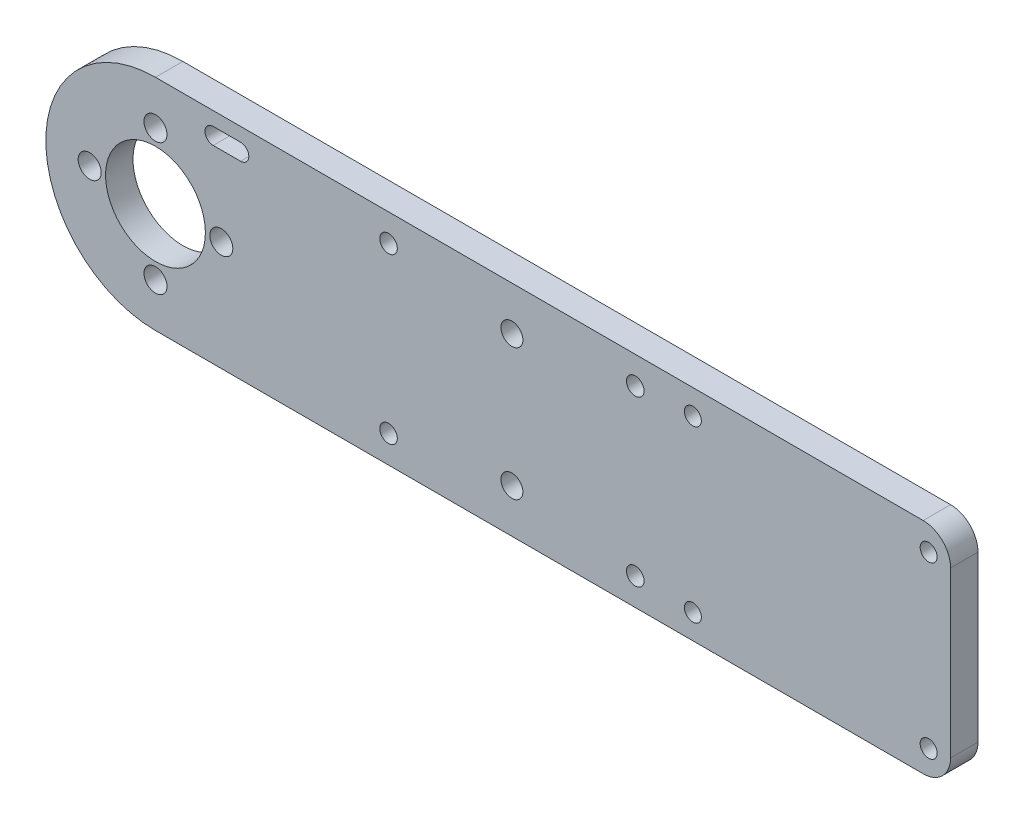
SolidWorks part; units mm, degrees
material "Acrylic (Medium-high impact)"
ref_plane "Front Plane" through (0, 0, 0) normal (0, 0, 1) x (1, 0, 0)
ref_plane "Top Plane" through (0, 0, 0) normal (0, 1, 0) x (1, 0, 0)
ref_plane "Right Plane" through (0, 0, 0) normal (1, 0, 0) x (0, 0, -1)
sketch "Sketch2" plane through (0, 0, 0) normal (0, 0, 1) x (1, 0, 0)
  line L0 (0, 20) -> (0, -20)
  line L1 (0, 20) -> (145, 20)
  line L2 (0, -20) -> (145, -20)
  line L3 (145, 20) -> (145, -20)
  line L4 (0, 0) -> (-20, 0)
  circle A0 centre (0, 0) radius 20
  circle A1 centre (0, 0) radius 9.1
  dimension "D1" = 40
  dimension "D3" = 18.2
  dimension "D2" = 165
extrude "Boss-Extrude1" add sketch "Sketch2" along normal mid plane 5 contours A1 L0 A0 | A0 L2 L3 L1 | A1 L4 A0 L0 | A1 L0 A0 L4 region at (9.696, 0, 0) region at (80.2769, 0, 0) region at (-9.696, 9.696, 0) region at (-9.696, -9.696, 0)
fillet "Fillet1" radius 5 2 edges at (145, -20, 0) (145, 20, 0)
sketch "Sketch3" plane through (0, 0, -2.5) normal (0, 0, -1) x (-1, 0, 0)
  line L0 (-119.5, 20) -> (-119.5, -20)
  line L1 (-119.5, 0) -> (-98, 0)
  line L2 (-98, 0) -> (-98, 15.5)
  line L3 (-145, 15) -> (-145, -15)
  line L4 (-140, -20) -> (0, -20)
  line L5 (0, 20) -> (-140, 20)
  line L6 (-145, 15) -> (-145, -15)
  line L7 (-140, -20) -> (0, -20)
  line L8 (0, 20) -> (-140, 20)
  line L9 (-119.5, 0) -> (-65, 0)
  line L10 (-65, 0) -> (-65, 15)
  line L11 (-65, 15) -> (-87.5, 15)
  line L12 (0, 0) -> (0, 12)
  line L13 (0, 0) -> (-65, 0)
  line L14 (-15.5185, 16) -> (-10.5185, 16) construction
  line L17 (-15.5185, 17.5) -> (-10.5185, 17.5)
  line L18 (-15.5185, 14.5) -> (-10.5185, 14.5)
  line L19 (0, 0) -> (18.4819, 0)
  line L20 (-65, 0.6163) -> (-65, 6.1951)
  line L21 (-65, 0) -> (-65, 12)
  circle A0 centre (0, 0) radius 12
  circle A1 centre (-98, 15.5) radius 1.55
  circle A2 centre (-98, -15.5) radius 1.55
  arc A3 (-145, -15) -> (-140, -20) centre (-140, -15) ccw
  arc A4 (0, -20) -> (0, 20) centre (0, 0) ccw
  arc A5 (-140, 20) -> (-145, 15) centre (-140, 15) ccw
  arc A6 (-145, -15) -> (-140, -20) centre (-140, -15) ccw
  arc A7 (0, -20) -> (0, 20) centre (0, 0) ccw
  arc A8 (-140, 20) -> (-145, 15) centre (-140, 15) ccw
  circle A9 centre (-141, -15.5) radius 1.55
  circle A10 centre (-141, 15.5) radius 1.55
  circle A11 centre (-87.5, 15) radius 1.6
  circle A12 centre (-87.5, -15) radius 1.6
  circle A13 centre (-42.5, -15) radius 1.6
  circle A14 centre (-42.5, 15) radius 1.6
  circle A15 centre (0, 12) radius 2.1
  circle A16 centre (12, 0) radius 2.1
  circle A17 centre (0, -12) radius 2.1
  circle A18 centre (-12, 0) radius 2.1
  arc A21 (-15.5185, 17.5) -> (-15.5185, 14.5) centre (-15.5185, 16) ccw
  arc A22 (-10.5185, 14.5) -> (-10.5185, 17.5) centre (-10.5185, 16) ccw
  circle A23 centre (-65, 12) radius 2
  circle A25 centre (-65, -12) radius 2
  point P35 (-13.0185, 16)
  point P48 (12, 0)
  point P53 (-12, 0)
  point P54 (0, -12)
  dimension "D2" = 24
  dimension "D6" = 3.1
  dimension "D10" = 3.2
  dimension "D11" = 4.2
  dimension "D13" = 65
  dimension "D17" = 65
  dimension "D18" = 4.2
  dimension "D12" = 4.2
  dimension "D19" = 4.2
  dimension "D21" = 4
  dimension "D3" = 21.5
  dimension "D4" = 15.5
  dimension "D5" = 98
  dimension "D7" = 27
  dimension "D8" = 15
  dimension "D9" = 22.5
  dimension "D14" = 5
  dimension "D15" = 3
  dimension "D16" = 4
  dimension "D20" = 12
  dimension "D1" = 0
extrude "Cut-Extrude1" cut sketch "Sketch3" against normal through all contours L19 A16 A0 | A0 A16 L19 | L19 A16 A0 | A0 A16 L19 | A0 A15 | A0 A15 L12 | L12 A15 A0 | A0 A18 L13 | L13 A18 A0 | A0 A18 L13 | L13 A18 A0 | A0 A17 | A0 A17 region at (12.8574, 0.9157, -2.5) region at (12.8574, -0.9157, -2.5) region at (11.0765, 0.8649, -2.5) region at (11.0765, -0.8649, -2.5) region at (0, 12.8574, -2.5) region at (0.8649, 11.0765, -2.5) region at (0, -11.0765, -2.5) region at (0, -12.8574, -2.5) region at (-0.8649, 11.0765, -2.5) region at (-11.0765, 0.8649, -2.5) region at (-11.0765, -0.8649, -2.5) region at (-12.8574, -0.9157, -2.5) region at (-12.8574, 0.9157, -2.5)
extrude "Cut-Extrude2" cut sketch "Sketch3<4>" against normal blind 10 contours L18 A22 L17 A21 | A12 | A11 | A13 | A14 | A10 | A9 | A1 | A2 | L21 A23 L10 | L10 A23 L21 | A25 region at (99.065, 16.565, -2.5) region at (89.0547, 15, -2.5) region at (65.8488, 12, -2.5) region at (64.1512, 12, -2.5) region at (13.0185, 16, -2.5) region at (98, -15.5, -2.5) region at (141, -15.5, -2.5) region at (141, 15.5, -2.5) region at (87.5, -15, -2.5) region at (42.5, -15, -2.5) region at (42.5, 15, -2.5) region at (65, -12, -2.5)
sketch "Sketch3<4>" plane through (0, 0, -2.5) normal (0, 0, -1) x (-1, 0, 0) same geometry as "Sketch3"
sketch "Sketch4" plane through (0, 0, -2.5) normal (0, 0, -1) x (-1, 0, 0)
  circle A0 centre (-42.5, 15) radius 2.5
  circle A1 centre (-42.5, -15) radius 2.5
  dimension "D1" = 5
  dimension "D2" = 5
extrude "Cut-Extrude3" cut sketch "Sketch4" against normal blind 2
